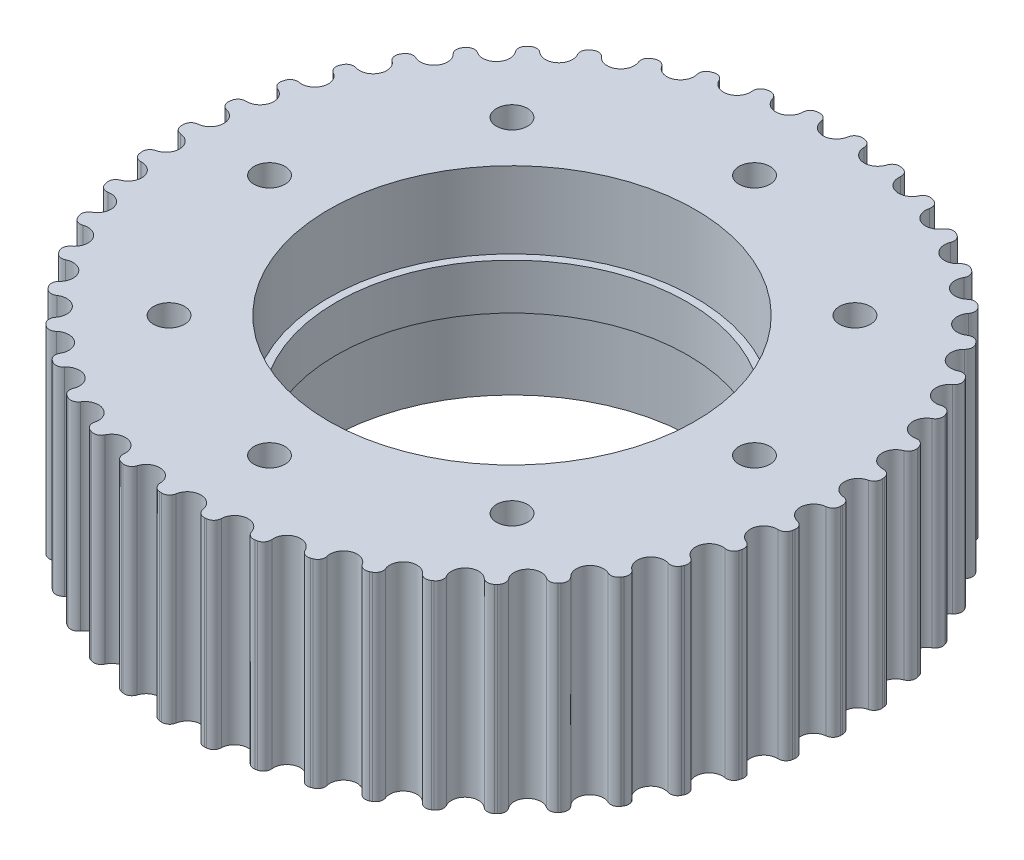
SolidWorks part; units mm, degrees
ref_plane "Front Plane" through (0, 0, 0) normal (0, 0, 1) x (1, 0, 0)
ref_plane "Top Plane" through (0, 0, 0) normal (0, 1, 0) x (1, 0, 0)
ref_plane "Right Plane" through (0, 0, 0) normal (1, 0, 0) x (0, 0, -1)
sketch "Sketch1" plane through (0, 0, 0) normal (0, 1, 0) x (1, 0, 0)
  line L0 (0, 0) -> (0, 21.582) construction
  line L1 (0, 0) -> (2.8938, 21.0541) construction
  circle A0 centre (0, 0) radius 21.582 construction
  circle A1 centre (0, 0) radius 20.362 construction
  circle A2 centre (0, 21.252) radius 0.89 construction
  circle A5 centre (2.8938, 21.0541) radius 0.89 construction
  arc A6 (0, 20.362) -> (0.8793, 21.1145) centre (0, 21.252) ccw
  arc A7 (0.8793, 21.1145) -> (1.4059, 21.5362) centre (1.3733, 21.0373) cw
  arc A8 (1.5397, 21.527) -> (2.004, 21.0376) centre (1.5041, 21.0283) cw
  arc A9 (2.7726, 20.1724) -> (2.004, 21.0376) centre (2.8938, 21.0541) cw
  arc A10 (1.4059, 21.5362) -> (1.5397, 21.527) centre (0, 0) cw
  arc A11 (0, 20.362) -> (2.7726, 20.1724) centre (0, 0) ccw
  dimension "D1" = 43.1641
  dimension "D3" = 1.78
  dimension "D4" = 0.5
  dimension "D2" = 1.22
  dimension "D5" = 7.826
extrude "Boss-Extrude1" add sketch "Sketch1" along normal mid plane 13 contours A6 A11 A9 A8 A7 region at (0.0017, 0, -0.025)
ref_axis "Axis1" through (0, 3.3, 0) along (0, -1, 0)
pattern_circular "CirPattern1" count 46 over 360 about axis through (0, 3.3, 0) along (0, -1, 0) of "Boss-Extrude1"
sketch "Sketch2" plane through (0, 0, 0) normal (1, 0, 0) x (0, 0, -1)
  line L10 (0, 6.5) -> (22.7568, 6.5) construction
  line L11 (0, 6.5) -> (0, 8.0875) construction
  line L12 (0, 8.0875) -> (22.7568, 8.0875) construction
  line L15 (22.7568, 6.5) -> (22.7568, 8.0875) construction
  line L20 (0, 3.3) -> (0, -3.3) construction
  line L22 (22.7568, 8.0875) -> (0, 8.0875)
  line L23 (22.7568, 8.0875) -> (22.7568, 6.5)
  line L24 (22.7568, 6.5) -> (0, 6.5)
  line L25 (0, 8.0875) -> (0, 6.5)
  dimension "D1" = 1.5875
  dimension "D2" = 22.7568
  dimension "D3" = 6.5
revolve "Revolve3" [suppressed] add sketch "Sketch2" angle 360 about axis through (0, 3.3, 0) along (0, -1, 0)
mirror "Mirror1" [suppressed] about plane through (0, 0, 0) normal (0, 1, 0)
sketch "Sketch3" plane through (0, 0, 0) normal (0, -1, 0) x (-1, 0, 0)
  circle A0 centre (0, 0) radius 11.5
  dimension "D1" = 23
extrude "Cut-Extrude1" cut sketch "Sketch3" against normal through all both and the other way through all
sketch "Sketch5" plane through (0, 0, 0) normal (0, 1, 0) x (1, 0, 0)
  line L0 (-15.875, 0) -> (0, 0) construction
  circle A0 centre (-15.875, 0) radius 1.016
  circle A1 centre (0, 0) radius 19.423 construction
  dimension "D1" = 2.032
  dimension "D2" = 38.8461
  dimension "D3" = 15.875
extrude "Cut-Extrude2" cut sketch "Sketch5" against normal through all both and the other way through all
pattern_circular "CirPattern2" count 8 over 360 about axis through (0, 3.3, 0) along (0, -1, 0) of "Cut-Extrude2"
sketch "Sketch8" plane through (0, 0, 0) normal (0, 1, 0) x (1, 0, 0)
  circle A0 centre (0, 0) radius 12
  dimension "D1" = 24
extrude "Cut-Extrude3" cut sketch "Sketch8" against normal blind 5 from surface starting at face at (-1.016, 6.5, -15.875)
extrude "Cut-Extrude4" cut sketch "Sketch8<2>" along normal blind 5 from surface starting at face at (-1.016, -6.5, -15.875)
sketch "Sketch8<2>" plane through (0, 0, 0) normal (0, 1, 0) x (1, 0, 0) same geometry as "Sketch8"
equation "\"TEETH_NUM\"= 46"
equation "\"TOOTH_PITCH\"= 3mm"
equation "\"PITCH_LINE_OFFSET\"= .015in"
equation "\"DIAMETER_PER_GROOVE\"= \"OUTSIDE_DIAMETER\" / \"TEETH_NUM\" * 1in"
equation "\"PITCH_DIAMETER\"= ( ( \"TEETH_NUM\" * 3 - 1.31 ) / 3.1415 + .415 ) * 1mm"
equation "\"OUTSIDE_DIAMETER\"= \"PITCH_DIAMETER\" - \"PITCH_LINE_OFFSET\" * 2"
equation "\"D1@Sketch1\"=\"OUTSIDE_DIAMETER\""
equation "\"TOOTH_HEIGHT\"= 1.22mm"
equation "\"D2@Sketch1\"=\"TOOTH_HEIGHT\""
equation "\"TOOTH_DIAMETER\"= 1.78mm"
equation "\"INTERNAL_RADIUS\"= .5mm"
equation "\"D3@Sketch1\"=\"TOOTH_DIAMETER\""
equation "\"D5@Sketch1\"=360 / \"TEETH_NUM\""
equation "\"D4@Sketch1\"=\"INTERNAL_RADIUS\""
equation "\"D1@CirPattern1\"=\"TEETH_NUM\""
equation "\"BELT_GAP\"= 13mm"
equation "\"D2@Sketch2\"=\"PITCH_DIAMETER\"/2+1/32"
equation "\"D3@Sketch2\"=\"BELT_GAP\"/2"
equation "\"D1@Sketch3\"=23mm"
equation "\"D1@Boss-Extrude1\"=\"BELT_GAP\""
equation "\"center_offset\"=0.75"
equation "\"Bearing_Diameter\"= 58mm"
equation "\"D2@Sketch5\"=\"PITCH_DIAMETER\"-0.2"
equation "\"Num_Interface_Holes\"= 8"
equation "\"D1@CirPattern2\"=\"Num_Interface_Holes\""
equation "\"D1@Cut-Extrude3\"=5mm"
